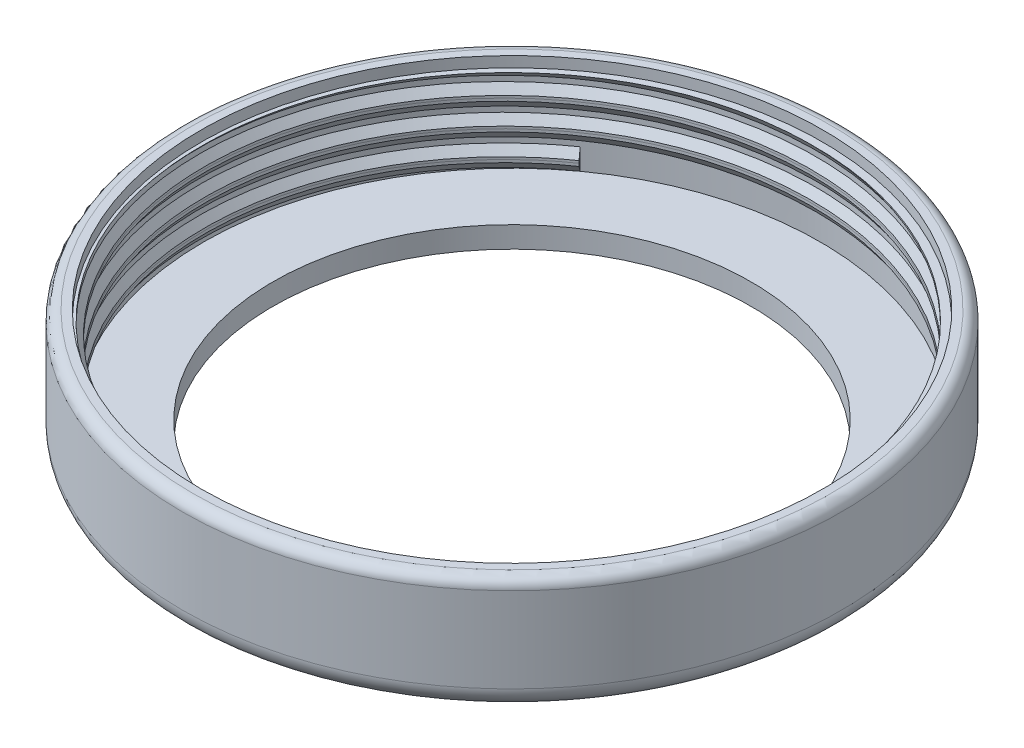
SolidWorks part; units mm, degrees
ref_plane "Front Plane" through (0, 0, 0) normal (0, 0, 1) x (1, 0, 0)
ref_plane "Top Plane" through (0, 0, 0) normal (0, 1, 0) x (1, 0, 0)
ref_plane "Right Plane" through (0, 0, 0) normal (1, 0, 0) x (0, 0, -1)
sketch "Sketch1" plane through (0, 0, 0) normal (0, 1, 0) x (1, 0, 0)
  circle A0 centre (0, 0) radius 31
  dimension "D1" = 62
extrude "Boss-Extrude1" add sketch "Sketch1" along normal blind 11 contours A0
shell "Shell1" thickness 2 removed face at (0, 11, 31)
sketch "Sketch2" plane through (0, 0, 0) normal (0, 1, 0) x (1, 0, 0)
  circle A0 centre (0, 0) radius 22.5
  dimension "D1" = 45
extrude "Cut-Extrude1" cut sketch "Sketch2" along normal up to surface (2 mm away) contours A0 up to face at (0, 2, 29)
ref_plane "Plane1" through (0, 14, 0) normal (0, 1, 0) x (1, 0, 0)
sketch "Sketch3" plane through (0, 14, 0) normal (0, 1, 0) x (1, 0, 0)
  circle A0 centre (0, 0) radius 29
  dimension "D1" = 58
curve "Helix/Spiral1" pitch 2.5 height 11 radius 29 centre (0, 14, 0) axis (0, -1, 0) start towards (0, 0, 1)
ref_plane "Plane2" through (0, 16, 0) normal (0, 1, 0) x (1, 0, 0)
sketch "Sketch8" plane through (0, 16, 0) normal (0, 1, 0) x (1, 0, 0)
  circle A0 centre (0, 0) radius 29.25
  dimension "D1" = 58.5
fillet "Fillet1" radius 2 1 edges at (0, 0, 31)
fillet "Fillet2" radius 1 1 edges at (0, 11, 31)
sketch "Sketch9" plane through (0, 0, 0) normal (1, 0, 0) x (0, 0, -1)
  line L0 (-29.0038, 14) -> (-29.0038, 19.5478) construction
  line L1 (-29.0038, 19.5478) -> (-29.0038, 14) construction
  line L2 (-29.0038, 14) -> (-29.0038, 12.9944) construction
  line L3 (-29.0038, 14) -> (-29.0038, 15)
  line L4 (-29.0038, 15) -> (-28.5038, 14.2165)
  line L5 (-28.5038, 14.2165) -> (-28.5038, 14)
  line L6 (-28.5038, 14) -> (-28.5038, 13.7399)
  line L7 (-28.5038, 13.7399) -> (-29.0038, 12.9944)
  line L8 (-29.0038, 12.9944) -> (-29.0038, 14)
  point P2 (0, 0)
  point P3 (0, 0)
  point P5 (0, 0)
  point P10 (0, 0)
  point P11 (0, 0)
  point P12 (0, 0)
  point P13 (0, 0)
  point P14 (0, 0)
  point P15 (0, 0)
  point P16 (0, 0)
  point P17 (0, 0)
  point P18 (0, 0)
  point P19 (0, 0)
  point P20 (-28.5038, 14.2165)
  dimension "D5" = 0.5
sweep "Sweep2" add profiles "Sketch9" path "Helix/Spiral1"
extrude "Cut-Extrude6" cut sketch "Sketch8" against normal blind 6 contours A0
